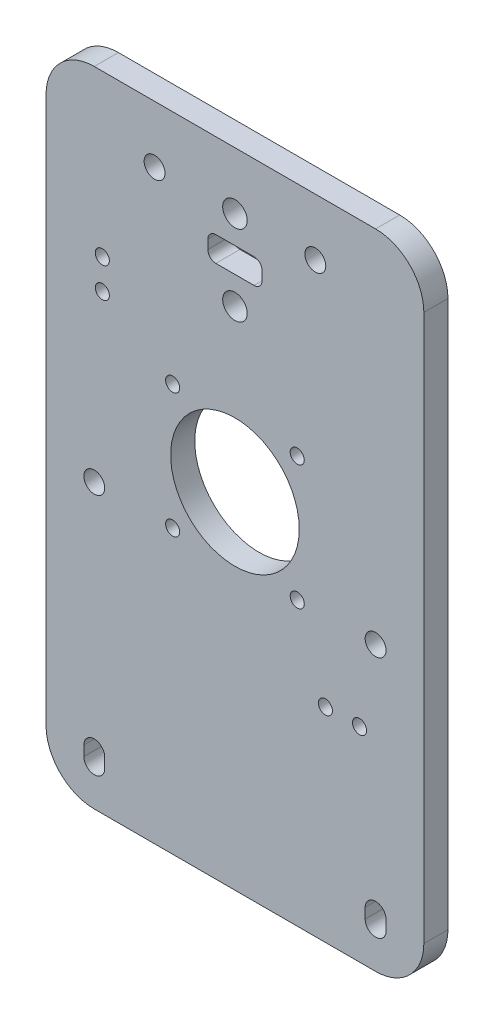
SolidWorks part; units mm, degrees
material "Polycarbonate (PC)"
ref_plane "Спереди" through (0, 0, 0) normal (0, 0, 1) x (1, 0, 0)
ref_plane "Сверху" through (0, 0, 0) normal (0, 1, 0) x (1, 0, 0)
ref_plane "Справа" through (0, 0, 0) normal (1, 0, 0) x (0, 0, -1)
sketch "Model" plane through (0, 0, 0) normal (0, 0, 1) x (1, 0, 0)
  line L0 (-2.3021, 85.8) -> (5.2264, 85.8) construction
  line L1 (6.75, 135.8) -> (-6.75, 135.8) construction
  line L5 (0, 27.6115) -> (0, 0) construction
  line L24 (-35, 64.9169) -> (-35, 77.3985) construction
  line L25 (-31.4983, 12.5) -> (-38.4, 12.5) construction
  line L26 (-31.4983, 10) -> (-38.4, 10) construction
  line L27 (-35, 12.5) -> (-35, 10) construction
  line L28 (-32.4, 12.5) -> (-32.4, 10)
  line L29 (-37.6, 12.5) -> (-37.6, 10)
  line L40 (31.4983, 10) -> (38.4, 10) construction
  line L41 (31.4983, 12.5) -> (38.4, 12.5) construction
  line L42 (35, 64.9169) -> (35, 77.3985) construction
  line L43 (35, 12.5) -> (35, 10) construction
  line L44 (32.4, 12.5) -> (32.4, 10)
  line L45 (37.6, 12.5) -> (37.6, 10)
  line L47 (-26.0102, 145.8) -> (26.0946, 145.8) construction
  line L48 (0, 129.408) -> (0, 90.7064) construction
  line L51 (-38.85, 70.45) -> (-29.8907, 70.45) construction
  line L53 (-16.3166, 125.8) -> (17.7871, 125.8) construction
  line L58 (38.85, 70.45) -> (29.8907, 70.45) construction
  line L4875 (-35, 160) -> (35, 160)
  line L4882 (47, 148) -> (47, 12)
  line L4889 (35, 0) -> (-35, 0)
  line L4896 (-47, 12) -> (-47, 148)
  line L5609 (6.75, 138.9) -> (-6.75, 138.9)
  line L5610 (-6.75, 138.9) -> (-6.75, 132.7)
  line L5611 (-6.75, 132.7) -> (6.75, 132.7)
  line L5612 (6.75, 132.7) -> (6.75, 138.9)
  line L6648 (-6.75, 138.9) -> (6.75, 138.9)
  line L6649 (6.75, 138.9) -> (6.75, 132.7)
  line L6650 (6.75, 132.7) -> (-6.75, 132.7)
  line L6651 (-6.75, 132.7) -> (-6.75, 138.9)
  arc A0 (-47, 12) -> (-35, 0) centre (-35, 12) ccw
  arc A1 (35, 0) -> (47, 12) centre (35, 12) ccw
  arc A2 (47, 148) -> (35, 160) centre (35, 148) ccw
  arc A3 (-35, 160) -> (-47, 148) centre (-35, 148) ccw
  circle A4 centre (0, 85.8) radius 16
  arc A13 (-32.4, 12.5) -> (-37.6, 12.5) centre (-35, 12.5) ccw
  arc A14 (-37.6, 10) -> (-32.4, 10) centre (-35, 10) ccw
  arc A19 (32.4, 12.5) -> (37.6, 12.5) centre (35, 12.5) cw
  arc A20 (37.6, 10) -> (32.4, 10) centre (35, 10) cw
  circle A29 centre (0, 145.8) radius 3.05
  circle A30 centre (-20, 145.8) radius 2.6
  circle A31 centre (20, 145.8) radius 2.6
  circle A32 centre (-35, 70.45) radius 2.6
  circle A33 centre (0, 125.8) radius 3.05
  circle A36 centre (35, 70.45) radius 2.6
  point P2 (-160.6279, 73.9855)
  point P3 (0, 0)
  point P17 (0, 0)
  point P23 (-35, 64.9169)
  point P77 (-35, 11.25)
  point P114 (35, 11.25)
  point P127 (0, 160)
  dimension "D5" = 32
  dimension "D8" = 94
  dimension "D30" = 5.2
  dimension "D33" = 5.2
  dimension "D35" = 6.1
  dimension "D14" = 12
  dimension "D3" = 160
  dimension "D6" = 60.45
  dimension "D7" = 74.2
  dimension "D9" = 70
  dimension "D10" = 24.2
  dimension "D12" = 20
  dimension "D13" = 20
  dimension "D16" = 2.5
  dimension "D17" = 10
  dimension "D18" = 5.2
  dimension "D25" = 14.2
  dimension "D34" = 20
  dimension "D41" = 13.5
  dimension "D42" = 6.2
extrude "Base" add sketch "Model" along normal blind 6 contours L4875 A3 L4896 A0 L4889 A1 L4882 A2 L45 A20 L44 A19 region at (0, 158.1443, 0)
fillet "FilletCableSlot" radius 2 4 edges at (6.75, 138.9, 3) (-6.75, 138.9, 3) (-6.75, 132.7, 3) (6.75, 132.7, 3)
hole_wizard "Ø3.2 (3.2) Stepper mount Holes" positions "Sketch6" profile "Sketch7" hole size "Ø3.5" standard "ANSI Metric" end condition through all
sketch "Sketch6" plane through (0, 0, 6) normal (0, 0, 1) x (1, 0, 0)
  line L2 (0, 0) -> (0, 95.4376) construction
  line L3 (35, 0) -> (-35, 0) construction
  point P0 (-15.5, 101.3)
  point P3 (-15.5, 70.3)
  point P6 (15.5, 70.3)
  point P9 (15.5, 101.3)
  dimension "D1" = 31
  dimension "D2" = 31
  dimension "D3" = 70.3
sketch "Sketch7" plane through (-15.5, 101.3, 6) normal (1, 0, 0) x (0, -1, 0)
  line L0 (0, 0) -> (0, 6)
  line L1 (0, 6) -> (1.75, 6)
  line L2 (1.75, 6) -> (1.75, 0)
  line L5 (1.75, 0) -> (0, 0)
  line L11 (0, -6.35) -> (0, 107.95) construction
  dimension "Thru Hole Dia." = 3.5
  dimension "Thru Hole Depth" = 6
hole_wizard "Ø3.5 (3.5) SensorMount" positions "Sketch8" profile "Sketch9" hole size "Ø3.5" standard "ANSI Metric" end condition through all
sketch "Sketch8" plane through (0, 0, 6) normal (0, 0, 1) x (1, 0, 0)
  line L0 (-35, 160) -> (35, 160) construction
  line L1 (-47, 12) -> (-47, 148) construction
  point P0 (-33, 120)
  point P2 (-33, 112.5)
  point P5 (0, 0)
  dimension "D1" = 7.5
  dimension "D2" = 40
  dimension "D3" = 14
sketch "Sketch9" plane through (-33, 120, 6) normal (1, 0, 0) x (0, -1, 0)
  line L0 (0, 0) -> (0, 6)
  line L1 (0, 6) -> (1.75, 6)
  line L2 (1.75, 6) -> (1.75, 0)
  line L5 (1.75, 0) -> (0, 0)
  line L11 (0, -6.35) -> (0, 107.95) construction
  dimension "Thru Hole Dia." = 3.5
  dimension "Thru Hole Depth" = 6
hole_wizard "Ø3.5 (3.5) CableMount" positions "Sketch10" profile "Sketch11" hole size "Ø3.5" standard "ANSI Metric" end condition through all
sketch "Sketch10" plane through (0, 0, 6) normal (0, 0, 1) x (1, 0, 0)
  line L0 (35, 0) -> (-35, 0) construction
  line L1 (47, 148) -> (47, 12) construction
  point P0 (22.5, 50.76)
  point P2 (31, 50.76)
  point P5 (0, 0)
  dimension "D1" = 8.5
  dimension "D2" = 50.76
  dimension "D3" = 16
sketch "Sketch11" plane through (22.5, 50.76, 6) normal (1, 0, 0) x (0, -1, 0)
  line L0 (0, 0) -> (0, 6)
  line L1 (0, 6) -> (1.75, 6)
  line L2 (1.75, 6) -> (1.75, 0)
  line L5 (1.75, 0) -> (0, 0)
  line L11 (0, -6.35) -> (0, 107.95) construction
  dimension "Thru Hole Dia." = 3.5
  dimension "Thru Hole Depth" = 6
